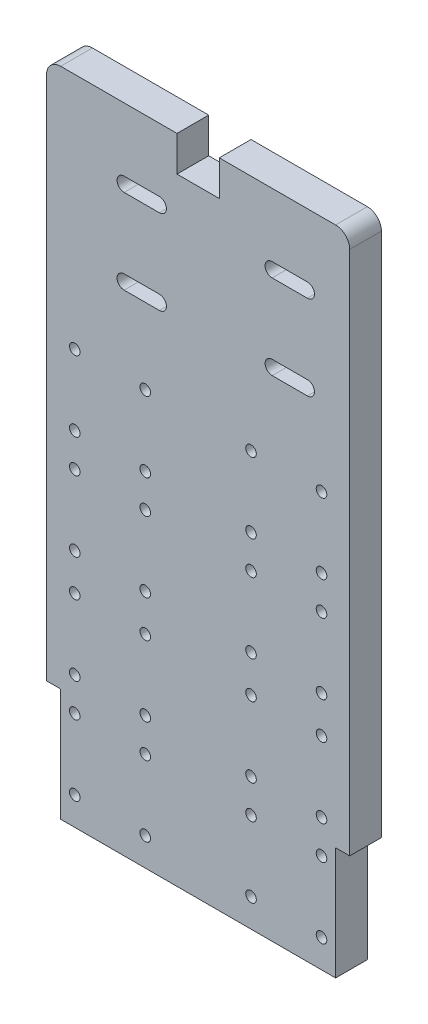
SolidWorks part; units mm, degrees
ref_plane "Front" through (0, 0, 0) normal (0, 0, 1) x (1, 0, 0)
ref_plane "Top" through (0, 0, 0) normal (0, 1, 0) x (1, 0, 0)
ref_plane "Right" through (0, 0, 0) normal (1, 0, 0) x (0, 0, -1)
sketch "Esquisse1" plane through (0, 0, 0) normal (0, 0, 1) x (1, 0, 0)
  line L1 (0, 0) -> (86, 0)
  line L2 (0, 0) -> (0, 185)
  line L3 (0, 185) -> (86, 185)
  line L4 (86, 0) -> (86, 185)
  dimension "D1" = 86
  dimension "D2" = 185
extrude "Boss.-Extru.1" add sketch "Esquisse1" along normal blind 9
sketch "Esquisse2" plane through (0, 0, 9) normal (0, 0, 1) x (1, 0, 0)
  line L0 (0, 47.5) -> (86, 47.5) construction
  line L1 (0, 185) -> (0, 0) construction
  line L2 (86, 0) -> (86, 185) construction
  line L3 (43, 47.5) -> (43, 77.5) construction
  line L4 (18, 47.5) -> (18, 38.434) construction
  line L5 (43, 77.5) -> (6.8221, 77.5) construction
  line L6 (18, 107.5) -> (18, 116.566) construction
  line L7 (0, 107.5) -> (86, 107.5) construction
  line L8 (0, 0) -> (86, 0) construction
  circle A0 centre (8, 57.5) radius 1.5
  circle A1 centre (28, 57.5) radius 1.5
  circle A2 centre (28, 37.5) radius 1.5
  circle A3 centre (8, 37.5) radius 1.5
  circle A4 centre (78, 37.5) radius 1.5
  circle A5 centre (58, 37.5) radius 1.5
  circle A6 centre (58, 57.5) radius 1.5
  circle A7 centre (78, 57.5) radius 1.5
  circle A8 centre (78, 97.5) radius 1.5
  circle A9 centre (58, 97.5) radius 1.5
  circle A10 centre (58, 117.5) radius 1.5
  circle A11 centre (78, 117.5) radius 1.5
  circle A12 centre (8, 117.5) radius 1.5
  circle A13 centre (28, 117.5) radius 1.5
  circle A14 centre (28, 97.5) radius 1.5
  circle A15 centre (8, 97.5) radius 1.5
  dimension "D1" = 20
  dimension "D2" = 20
  dimension "D3" = 3
  dimension "D4" = 25
  dimension "D5" = 40
  dimension "D6" = 47.5
extrude "Enlèv. mat.-Extru.1" cut sketch "Esquisse2" against normal through all
sketch "Esquisse3" plane through (0, 0, 9) normal (0, 0, 1) x (1, 0, 0)
  line L0 (43, 0) -> (43, 185) construction
  line L1 (0, 0) -> (86, 0) construction
  line L2 (86, 185) -> (0, 185) construction
  line L3 (43, 18) -> (1.3662, 18) construction
  line L4 (18, 18) -> (18, 55.2921) construction
  line L5 (43, 48) -> (3.2443, 48) construction
  line L6 (18, 78) -> (18, 40.7079) construction
  line L7 (68, 78) -> (68, 40.7079) construction
  line L8 (68, 18) -> (68, 55.2921) construction
  circle A0 centre (8, 28) radius 1.5
  circle A1 centre (8, 8) radius 1.5
  circle A2 centre (28, 8) radius 1.5
  circle A3 centre (28, 28) radius 1.5
  circle A4 centre (28, 68) radius 1.5
  circle A5 centre (28, 88) radius 1.5
  circle A6 centre (8, 88) radius 1.5
  circle A7 centre (8, 68) radius 1.5
  circle A8 centre (78, 68) radius 1.5
  circle A9 centre (78, 88) radius 1.5
  circle A10 centre (58, 88) radius 1.5
  circle A11 centre (58, 68) radius 1.5
  circle A12 centre (58, 28) radius 1.5
  circle A13 centre (58, 8) radius 1.5
  circle A14 centre (78, 8) radius 1.5
  circle A15 centre (78, 28) radius 1.5
  dimension "D1" = 20
  dimension "D6" = 3
  dimension "D2" = 20
  dimension "D3" = 25
  dimension "D4" = 60
  dimension "D5" = 18
extrude "Enlèv. mat.-Extru.2" cut sketch "Esquisse3" against normal through all
sketch "Esquisse4" plane through (0, 0, 9) normal (0, 0, 1) x (1, 0, 0)
  line L0 (43, 0) -> (43, 48.0891) construction
  line L1 (0, 0) -> (4, 0)
  line L2 (0, 0) -> (0, 32)
  line L3 (0, 32) -> (4, 32)
  line L4 (4, 0) -> (4, 32)
  line L5 (0, 0) -> (86, 0) construction
  line L6 (82, 0) -> (82, 32)
  line L7 (86, 32) -> (82, 32)
  line L8 (86, 0) -> (86, 32)
  line L9 (86, 0) -> (82, 0)
  dimension "D1" = 4
  dimension "D2" = 32
extrude "Enlèv. mat.-Extru.3" cut sketch "Esquisse4" against normal through all
sketch "Esquisse6" plane through (0, 0, 9) normal (0, 0, 1) x (1, 0, 0)
  line L0 (22, 165) -> (32, 165) construction
  line L1 (22, 167) -> (32, 167)
  line L2 (22, 163) -> (32, 163)
  line L3 (27, 165) -> (27, 153) construction
  line L4 (27, 153) -> (48, 153) construction
  line L5 (22, 141) -> (32, 141) construction
  line L6 (22, 139) -> (32, 139)
  line L7 (22, 143) -> (32, 143)
  line L8 (48, 153) -> (48, 155.9774) construction
  line L9 (74, 165) -> (64, 165) construction
  line L10 (74, 167) -> (64, 167)
  line L11 (74, 163) -> (64, 163)
  line L12 (74, 141) -> (64, 141) construction
  line L13 (74, 139) -> (64, 139)
  line L14 (74, 143) -> (64, 143)
  line L15 (0, 185) -> (0, 32) construction
  arc A0 (22, 167) -> (22, 163) centre (22, 165) ccw
  arc A1 (32, 163) -> (32, 167) centre (32, 165) ccw
  arc A2 (22, 139) -> (22, 143) centre (22, 141) cw
  arc A3 (32, 143) -> (32, 139) centre (32, 141) cw
  arc A4 (74, 167) -> (74, 163) centre (74, 165) cw
  arc A5 (64, 163) -> (64, 167) centre (64, 165) cw
  arc A6 (74, 139) -> (74, 143) centre (74, 141) ccw
  arc A7 (64, 143) -> (64, 139) centre (64, 141) ccw
  circle A8 centre (28, 117.5) radius 1.5 construction
  point P2 (27, 165)
  point P12 (27, 141)
  point P22 (69, 165)
  point P29 (69, 141)
  dimension "D1" = 4
  dimension "D2" = 10
  dimension "D3" = 42
  dimension "D4" = 24
  dimension "D5" = 35.5
  dimension "D6" = 22
extrude "Enlèv. mat.-Extru.4" cut sketch "Esquisse6" against normal through all
sketch "Esquisse7" plane through (0, 0, 9) normal (0, 0, 1) x (1, 0, 0)
  line L0 (43, 185) -> (43, 175) construction
  line L1 (86, 185) -> (0, 185) construction
  line L2 (49, 175) -> (37, 175)
  line L3 (37, 175) -> (37, 185)
  line L4 (37, 185) -> (49, 185)
  line L5 (49, 175) -> (49, 185)
  dimension "D1" = 12
  dimension "D2" = 10
extrude "Enlèv. mat.-Extru.5" cut sketch "Esquisse7" against normal through all
fillet "Congé1" radius 4 2 edges at (86, 185, 4.5) (0, 185, 4.5)
